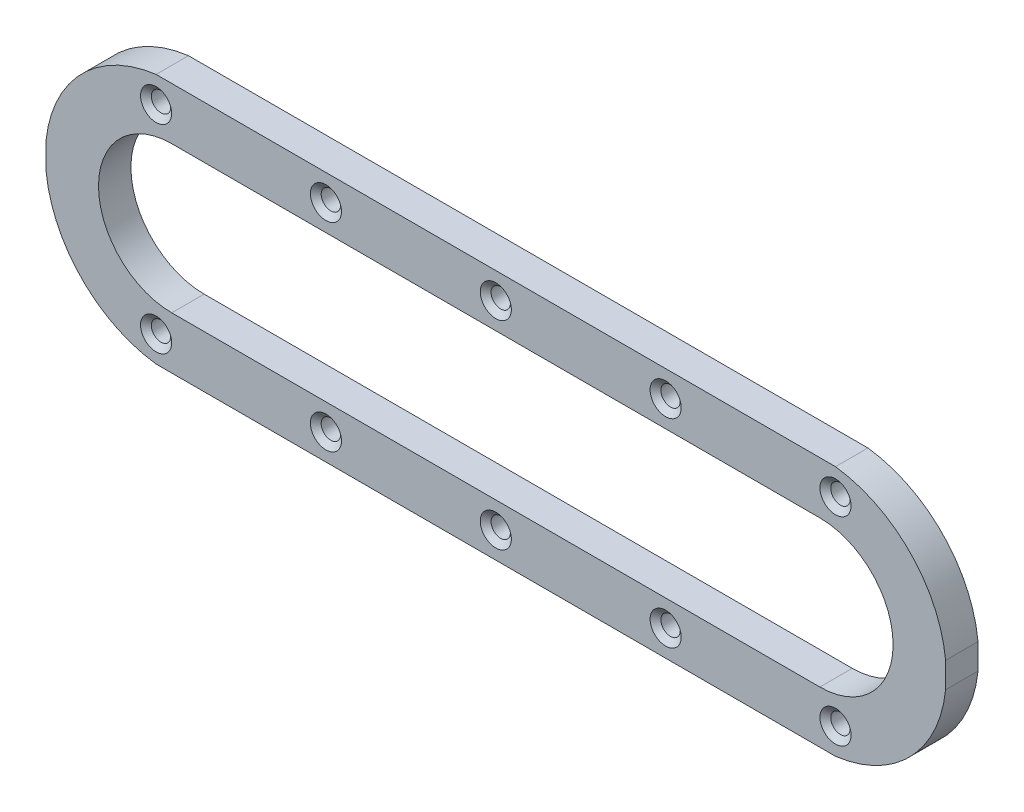
SolidWorks part; units mm, degrees
ref_plane "Front" through (0, 0, 0) normal (0, 0, 1) x (1, 0, 0)
ref_plane "Top" through (0, 0, 0) normal (0, 1, 0) x (1, 0, 0)
ref_plane "Right" through (0, 0, 0) normal (1, 0, 0) x (0, 0, -1)
sketch "Sketch1" plane through (0, 0, 0) normal (0, 0, 1) x (1, 0, 0)
  line L1 (88.138, 24.5745) -> (-88.138, 24.5745)
  line L2 (88.138, 24.5745) -> (88.138, -24.5745)
  line L3 (88.138, -24.5745) -> (-88.138, -24.5745)
  line L4 (-88.138, 24.5745) -> (-88.138, -24.5745)
  line L5 (88.138, 24.5745) -> (-88.138, -24.5745) construction
  line L6 (88.138, -24.5745) -> (-88.138, 24.5745) construction
  point P0 (0, 0)
  dimension "D1" = 176.276
  dimension "D2" = 49.149
extrude "Boss-Extrude1" add sketch "Sketch1" along normal blind 6.35
sketch "Sketch2" plane through (0, 0, 6.35) normal (0, 0, 1) x (1, 0, 0)
  line L0 (63.5, 0) -> (-63.5, 0) construction
  line L1 (63.5, -14.351) -> (-63.5, -14.351)
  line L2 (63.5, 14.351) -> (-63.5, 14.351)
  arc A0 (63.5, -14.351) -> (63.5, 14.351) centre (63.5, 0) ccw
  arc A1 (-63.5, 14.351) -> (-63.5, -14.351) centre (-63.5, 0) ccw
  point P2 (0, 0)
  dimension "D1" = 127
  dimension "D2" = 28.702
extrude "Cut-Extrude1" cut sketch "Sketch2" against normal through all
sketch "Sketch8" plane through (0, 0, 6.35) normal (0, 0, 1) x (1, 0, 0)
  line L4 (-63.5, 24.765) -> (63.5, 24.765)
  line L5 (-63.5, 14.351) -> (63.5, 14.351)
  line L6 (-63.5, -14.351) -> (63.5, -14.351)
  line L7 (-63.5, -24.765) -> (63.5, -24.765)
  arc A5 (-63.5, 14.351) -> (-63.5, -14.351) centre (-63.5, 0) ccw
  arc A6 (-63.5, 24.765) -> (-63.5, -24.765) centre (-63.5, 0) ccw
  arc A7 (63.5, 14.351) -> (63.5, -14.351) centre (63.5, 0) cw
  arc A8 (63.5, 24.765) -> (63.5, -24.765) centre (63.5, 0) cw
  line M5 (-88.138, 24.5745) -> (-88.138, -24.5745)
  line M6 (-88.138, -24.5745) -> (88.138, -24.5745)
  line M7 (88.138, -24.5745) -> (88.138, 24.5745)
  line M8 (88.138, 24.5745) -> (-88.138, 24.5745)
  dimension "D1" = 10.414
  dimension "D2" = 10.414
extrude "Cut-Extrude4" cut sketch "Sketch8" against normal through all contours A6 M8 M5 | A6 M5 M6 | A8 M8 M7 | A8 M7 M6 region at (-82.8086, 19.1871, 6.35) region at (82.8086, 19.1871, 6.35) region at (-82.8086, -19.1871, 6.35) region at (82.8086, -19.1871, 6.35)
sketch "Sketch12" plane through (0, 0, 6.35) normal (0, 0, 1) x (1, 0, 0)
  circle A0 centre (-33.2829, 19.4627) radius 2.5527
  circle A1 centre (-66.5658, 19.4627) radius 2.5527
  circle A2 centre (0, 19.4627) radius 2.5527
  circle A3 centre (66.5658, 19.4627) radius 2.5527
  circle A4 centre (33.2829, 19.4628) radius 2.5527
  circle A5 centre (0, -19.4627) radius 2.5527
  circle A6 centre (-33.2829, -19.4627) radius 2.5527
  circle A7 centre (-66.5658, -19.4627) radius 2.5527
  circle A8 centre (33.2829, -19.4627) radius 2.5527
  circle A9 centre (66.5658, -19.4627) radius 2.5527
  dimension "D1" = 5.1054
hole_wizard "#10-24 Tapped Hole1" positions "Sketch15" profile "Sketch16" tap size "#10-24" standard "ANSI Inch" end condition through all
sketch "Sketch15" plane through (0, 0, 6.35) normal (0, 0, 1) x (1, 0, 0)
  point P0 (-66.5658, 19.4627)
  point P3 (-33.2829, 19.4627)
  point P6 (0, 19.4627)
  point P9 (33.2829, 19.4628)
  point P12 (66.5658, 19.4627)
  point P15 (66.5658, -19.4627)
  point P18 (33.2829, -19.4627)
  point P21 (0, -19.4627)
  point P24 (-33.2829, -19.4627)
  point P27 (-66.5658, -19.4627)
sketch "Sketch16" plane through (-66.5658, 19.4627, 6.35) normal (1, 0, 0) x (0, -1, 0)
  line L0 (0, 0) -> (0, 6.35)
  line L1 (0, 6.35) -> (1.8986, 6.35)
  line L2 (1.8986, 6.35) -> (1.8986, 0.9644)
  line L3 (1.8986, 0.9644) -> (3.048, 0)
  line L5 (3.048, 0) -> (0, 0)
  line L6 (-1.8986, 0.9644) -> (-3.048, 0) construction
  line L11 (0, -6.35) -> (0, 107.95) construction
  dimension "Thread Major Dia." = 3.7973
  dimension "Thru Tap Drill Depth" = 6.35
  dimension "Near C'Sink Dia." = 6.096
  dimension "Near C'Sink Angle" = 100
